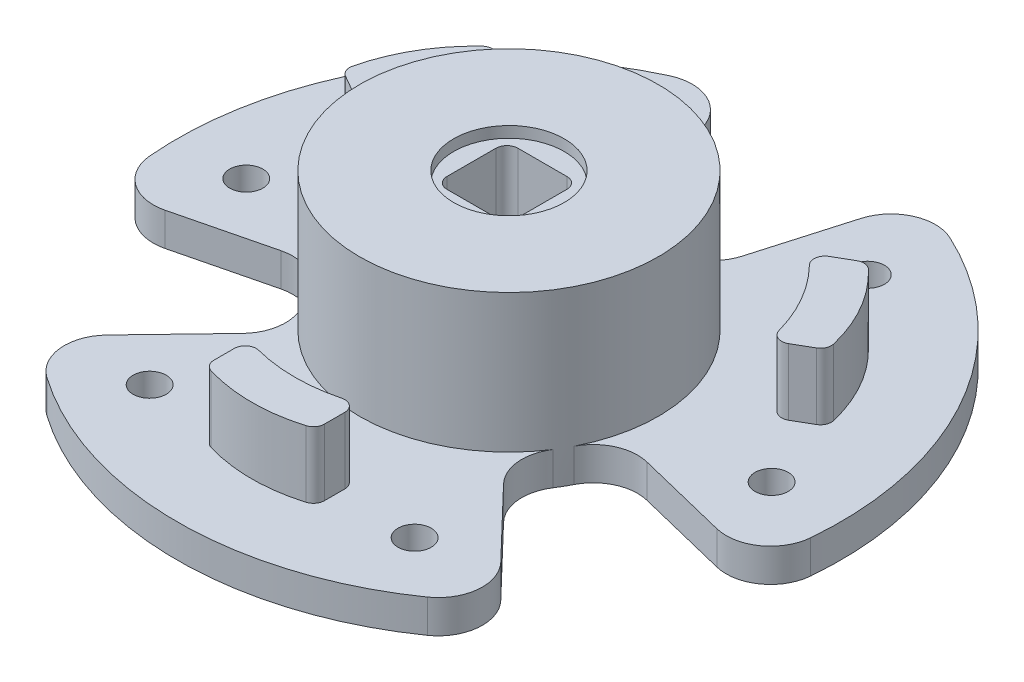
SolidWorks part; units mm, degrees
ref_plane "Front Plane" through (0, 0, 0) normal (0, 0, 1) x (1, 0, 0)
ref_plane "Top Plane" through (0, 0, 0) normal (0, 1, 0) x (1, 0, 0)
ref_plane "Right Plane" through (0, 0, 0) normal (1, 0, 0) x (0, 0, -1)
sketch "Sketch1" plane through (0, 0, 0) normal (0, 1, 0) x (1, 0, 0)
  circle A0 centre (0, 0) radius 30
extrude "Boss-Extrude1" add sketch "Sketch1" along normal blind 2.5 and the other way blind 0.5 contours A0
sketch "Sketch2" plane through (0, 2.5, 0) normal (0, 1, 0) x (1, 0, 0)
  circle A0 centre (0, 0) radius 13.5
extrude "Boss-Extrude2" add sketch "Sketch2" along normal blind 12.5
sketch "Sketch3" plane through (0, 15, 0) normal (0, 1, 0) x (1, 0, 0)
  line L6 (0, 30) -> (0, -30) construction
  line L7 (-30, 0) -> (30, 0) construction
  circle A1 centre (0, 0) radius 30 construction
  circle A2 centre (0, 0) radius 5
sketch "Sketch4" plane through (0, 15, 0) normal (0, 1, 0) x (1, 0, 0)
  line L2 (-3.3468, 3.1621) -> (3.0832, 3.1621)
  line L3 (-3.3468, 3.1621) -> (-3.3468, -3.2679)
  line L4 (-3.3468, -3.2679) -> (3.0832, -3.2679)
  line L5 (3.0832, 3.1621) -> (3.0832, -3.2679)
  dimension "D1" = 6.43
  dimension "D2" = 6.43
extrude "Cut-Extrude2" cut sketch "Sketch4" against normal blind 17.5 contours L2 L5 L4 L3
fillet "Fillet1" radius 1 4 edges at (3.0832, 7.25, 3.2679) (3.0832, 7.25, -3.1621) (-3.3468, 7.25, -3.1621) (-3.3468, 7.25, 3.2679)
extrude "Cut-Extrude3" cut sketch "Sketch3" against normal blind 1 contours A2
sketch "Sketch5" plane through (0, 2.5, 0) normal (0, 1, 0) x (1, 0, 0)
  line L1 (-30, 0) -> (30, 0) construction
  line L2 (0, 0) -> (-15, 25.9808) construction
  line L3 (0, 0) -> (15, 25.9808) construction
  line L4 (0, 0) -> (30, 0) construction
  line L5 (0, 0) -> (-15, -25.9808) construction
  line L6 (0, 0) -> (15, -25.9808) construction
  circle A0 centre (0, 0) radius 30 construction
  dimension "D1" = 60
  dimension "D2" = 60
  dimension "D3" = 60
  dimension "D4" = 60
  dimension "D5" = 60
sketch "Sketch6" plane through (0, 2.5, 0) normal (0, 1, 0) x (1, 0, 0)
  line L0 (0, 0) -> (-15, 25.9808) construction
  line L1 (0, 0) -> (15, 25.9808) construction
  line L2 (-30, 0) -> (30, 0) construction
  circle A0 centre (-11.875, 20.5681) radius 1.5
  circle A1 centre (11.875, 20.5681) radius 1.5
  circle A2 centre (23.75, 0) radius 1.5
  circle A3 centre (-23.75, 0) radius 1.5
  circle A4 centre (-11.9788, -20.5078) radius 1.5
  circle A5 centre (11.9788, -20.5078) radius 1.5
  dimension "D1" = 23.75
  dimension "D2" = 23.75
  dimension "D4" = 23.75
  dimension "D5" = 23.75
  dimension "D3" = 23.75
  dimension "D6" = 23.75
extrude "Cut-Extrude4" cut sketch "Sketch6" against normal blind 6
sketch "Sketch7" plane through (0, 2.5, 0) normal (0, 1, 0) x (1, 0, 0)
  line L0 (-8.353, 28.8137) -> (-3.7589, 12.9661)
  line L1 (8.353, 28.8137) -> (3.7589, 12.9661)
  circle A0 centre (0, 0) radius 30 construction
  circle A1 centre (0, 0) radius 13.5 construction
  arc A2 (-8.353, 28.8137) -> (8.353, 28.8137) centre (0, 0) cw
  arc A3 (-3.7589, 12.9661) -> (3.7589, 12.9661) centre (0, 0) cw
extrude "Cut-Extrude5" cut sketch "Sketch7" against normal blind 6
fillet "Fillet2" radius 4 4 edges at (-8.353, 1, -28.8137) (8.353, 1, -28.8137) (3.7589, 1, -12.9661) (-3.7589, 1, -12.9661)
pattern_circular "CirPattern1" count 3 over 360 about axis through (0, 15, 0) along (0, 1, 0) of "Cut-Extrude5", "Fillet2"
sketch "Sketch9" plane through (0, 2.5, 0) normal (0, 1, 0) x (1, 0, 0)
  line L0 (0, -13.5) -> (7.7942, -13.5) construction
  line L1 (0, 0) -> (15, -25.9808) construction
  line L2 (7.7942, -13.5) -> (-7.7942, -13.5) construction
  line L3 (0, 0) -> (-15, -25.9808) construction
  line L4 (0, -13.5) -> (0, -18.5) construction
  line L5 (0, -18.5) -> (-4.9956, -18.5) construction
  line L6 (-4.9956, -18.5) -> (5.0044, -18.5) construction
  line L8 (5.0044, -18.5) -> (5.0044, -22.4106)
  line L10 (-4.9956, -22.4106) -> (-4.9956, -18.5)
  arc A0 (-11.328, -7.3435) -> (11.328, -7.3435) centre (0, 0) ccw construction
  arc A1 (-4.9956, -18.5) -> (5.0044, -18.5) centre (0.0044, -4.3579) ccw
  arc A2 (-4.9956, -22.4106) -> (5.0044, -22.4106) centre (0.0044, -8.2684) ccw
  dimension "D1" = 10
extrude "Boss-Extrude3" add sketch "Sketch9" along normal blind 6
fillet "Fillet3" radius 1 4 edges at (5.0044, 5.5, 18.5) (5.0044, 5.5, 22.4106) (-4.9956, 5.5, 22.4106) (-4.9956, 5.5, 18.5)
pattern_circular "CirPattern2" count 3 over 360 about axis through (0, 15, 0) along (0, 1, 0) of "Boss-Extrude3", "Fillet3"
